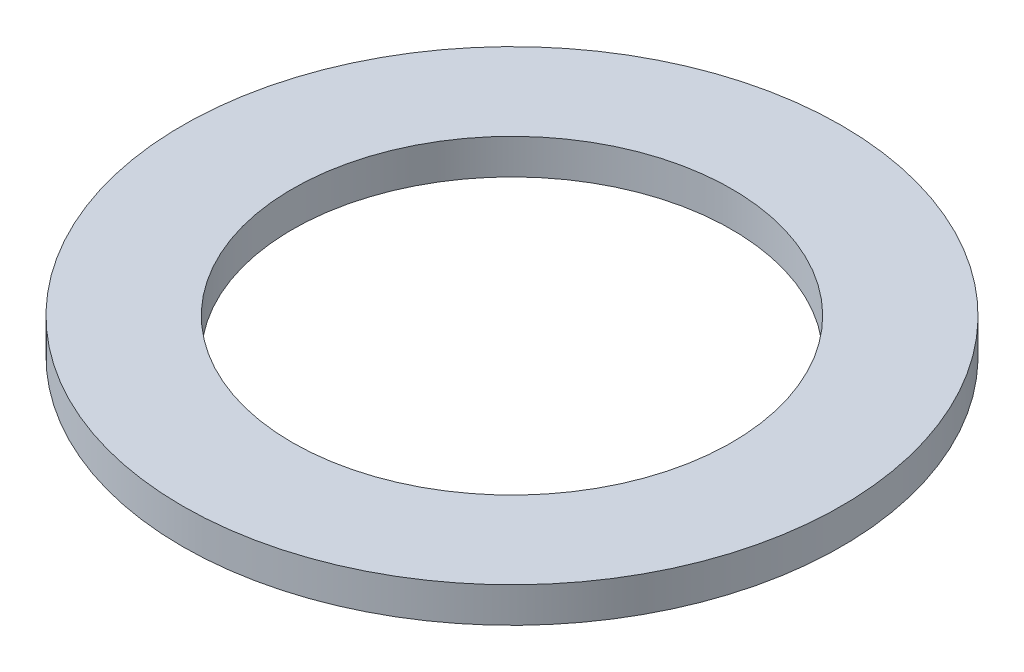
SolidWorks part; units mm, degrees
ref_plane "Front Plane" through (0, 0, 0) normal (0, 0, 1) x (1, 0, 0)
ref_plane "Top Plane" through (0, 0, 0) normal (0, 1, 0) x (1, 0, 0)
ref_plane "Right Plane" through (0, 0, 0) normal (1, 0, 0) x (0, 0, -1)
sketch "Sketch1" plane through (0, 0, 0) normal (0, 1, 0) x (1, 0, 0)
  circle A0 centre (0, 0) radius 75
  dimension "FLANGE_OD" = 150
extrude "Boss-Extrude1" add sketch "Sketch1" along normal blind 8
sketch "Sketch2" plane through (0, 0, 0) normal (0, 1, 0) x (1, 0, 0)
  circle A0 centre (0, 0) radius 50
  dimension "BORE_D" = 100
extrude "Cut-Extrude1" cut sketch "Sketch2" along normal through all
sketch "Sketch3" plane through (0, 8, 0) normal (0, 1, 0) x (1, 0, 0)
  circle A0 centre (0, 0) radius 30.6274 construction
  circle A1 centre (-30.6274, 0) radius 2.9062
  dimension "BOLT_D" = 5.8124
  dimension "BOLT_PCD" = 61.2548
extrude "Cut-Extrude2" cut sketch "Sketch3" against normal blind 5.2586 rebuild error yes
pattern_circular "CirPattern1" count 5 over 360 rebuild error yes
